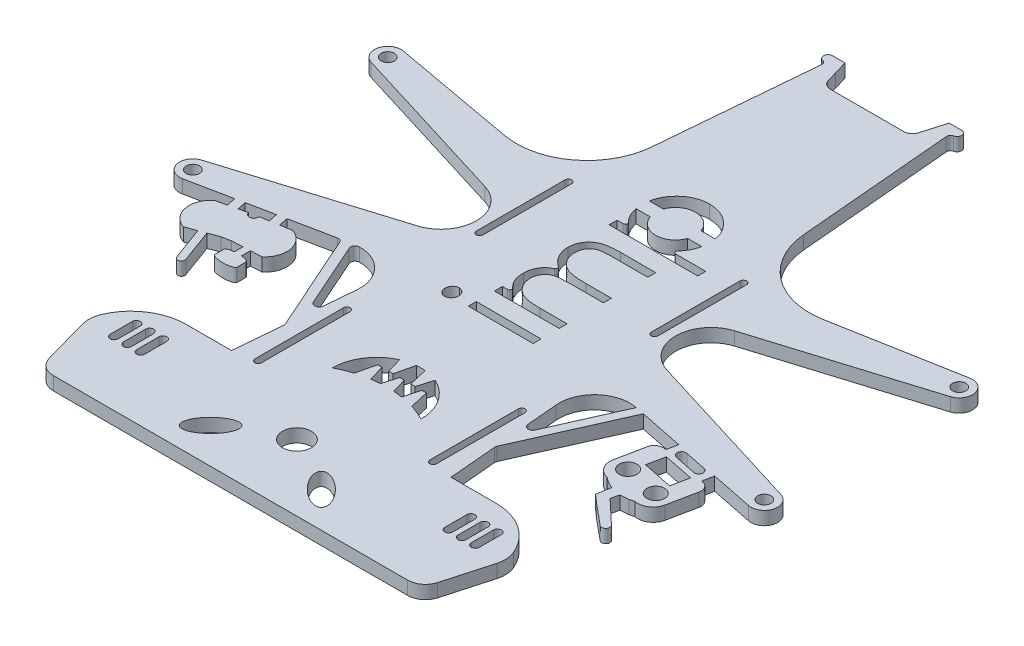
SolidWorks part; units mm, degrees
ref_plane "前视基准面" through (0, 0, 0) normal (0, 0, 1) x (1, 0, 0)
ref_plane "上视基准面" through (0, 0, 0) normal (0, 1, 0) x (1, 0, 0)
ref_plane "右视基准面" through (0, 0, 0) normal (1, 0, 0) x (0, 0, -1)
sketch "草图1" plane through (0, 0, 0) normal (0, 1, 0) x (1, 0, 0)
  line L5 (-65.3843, -19.1333) -> (-28.1418, -7.6445)
  line L6 (-63.9021, -24.9398) -> (-56.5526, -23.4451)
  line L8 (0, 0) -> (0, 91.5573) construction
  line L9 (0, 0) -> (-115.8836, 0) construction
  line L15 (0, 0) -> (0, -124.2991) construction
  line L16 (-15, -65) -> (15, -65) construction
  line L20 (-15.42, -115) -> (17.43, -115) construction
  line L21 (-28, -109.5) -> (-28, -90)
  line L22 (28, -109.5) -> (28, -90)
  line L23 (-17.5, -120) -> (17.5, -120)
  line L28 (22.5, -27) -> (22.5, 27) construction
  line L29 (-22.5, -27) -> (-22.5, 27) construction
  line L30 (28.1418, -7.6445) -> (65.3843, -19.1333)
  line L31 (28.1418, 7.6445) -> (65.3843, 19.1333)
  line L32 (-28, -90) -> (28, -90) construction
  line L33 (28, -90) -> (22.5, -27)
  line L34 (-28, -90) -> (-22.5, -27)
  line L36 (0, 0) -> (104.501, 0) construction
  line L37 (-28.1418, 7.6445) -> (-65.3843, 19.1333)
  line L39 (22.5, 70) -> (22.5, 27) construction
  line L40 (-22.5, 70) -> (-22.5, 27) construction
  line L41 (31.9307, 19.129) -> (63.9635, 24.9516) construction
  line L42 (-63.9635, 24.9516) -> (-31.9307, 19.129) construction
  line L43 (-17.1562, 34.2114) -> (-14.0779, 69.4717)
  line L44 (63.9635, 24.9516) -> (35.957, 19.8608)
  line L45 (-63.9635, 24.9516) -> (-35.957, 19.8608)
  line L46 (17.1562, 34.2114) -> (14.0779, 69.4717)
  line L51 (-49.203, -21.9504) -> (-47.2101, -31.7498) construction
  line L58 (-48.19, -31.9491) -> (-46.2301, -31.5505)
  line L59 (-41.8535, -20.4557) -> (-32.0641, -18.4647)
  line L65 (-14.4088, 65.6811) -> (14.4088, 65.6811) construction
  line L70 (-10.8845, 69.4717) -> (-10.1819, 67.1107)
  line L75 (10.8788, 69.4717) -> (10.1832, 67.115)
  line L76 (-8.265, 65.6811) -> (8.265, 65.6811)
  line L77 (-56.5526, -23.4451) -> (-41.8535, -20.4557) construction
  line L78 (-46.2301, -31.5505) -> (-43.7558, -31.4316)
  line L79 (-48.19, -31.9491) -> (-50.5246, -32.81)
  line L80 (-54.3603, -34.2244) -> (-39.6612, -31.235) construction
  line L81 (-48.7048, -24.4002) -> (-49.7844, -24.1095) construction
  line L82 (-48.7048, -24.4002) -> (-47.8245, -23.711) construction
  line L84 (41.8535, -20.4557) -> (32.0641, -18.4647)
  line L101 (-49.7844, -24.1095) -> (-47.8245, -23.711) construction
  line L103 (63.9021, -24.9398) -> (56.5526, -23.4451)
  line L106 (41.8535, -20.4557) -> (56.5526, -23.4451) construction
  line L107 (42.3935, -35.3623) -> (50.233, -36.9567) construction
  line L108 (39.6612, -31.235) -> (40.9566, -24.8654)
  line L109 (43.3151, -23.3041) -> (43.6091, -23.3639)
  line L110 (54.3603, -34.2244) -> (55.6557, -27.8548)
  line L111 (38.9637, -34.6648) -> (56.0543, -25.8949) construction
  line L112 (41.3552, -22.9055) -> (53.6628, -37.6542) construction
  line L113 (49.203, -21.9504) -> (41.4195, -60.2218) construction
  line L114 (43.6091, -23.3639) -> (44.8847, -23.1131) construction
  line L115 (44.8847, -23.1131) -> (52.7242, -24.7074) construction
  line L116 (52.7242, -24.7074) -> (53.8005, -25.4366) construction
  line L117 (53.8005, -25.4366) -> (54.0944, -25.4964)
  line L120 (44.938, -36.9003) -> (47.2899, -37.3786) construction
  line L121 (45.4995, -45.1782) -> (43.5396, -44.7797) construction
  line L122 (45.4995, -45.1782) -> (47.2899, -37.3786) construction
  line L123 (43.5396, -44.7797) -> (44.938, -36.9003) construction
  line L124 (43.2738, -36.0516) -> (49.1534, -37.2474) construction
  line L125 (47.2899, -37.3786) -> (49.1534, -37.2474)
  line L126 (44.938, -36.9003) -> (43.2738, -36.0516)
  line L127 (43.2738, -36.0516) -> (42.3935, -35.3623)
  line L128 (49.1534, -37.2474) -> (50.233, -36.9567)
  line L129 (43.1907, -31.4426) -> (51.0302, -33.0369) construction
  line L130 (40.7168, -24.8097) -> (55.8983, -27.8973) construction
  line L131 (52.7242, -24.7074) -> (53.1228, -22.7476) construction
  line L132 (44.8847, -23.1131) -> (45.2833, -21.1532) construction
  line L133 (53.1228, -22.7476) -> (56.5526, -23.4451) construction
  line L134 (41.8535, -20.4557) -> (45.2833, -21.1532) construction
  line L135 (45.6157, -39.5893) -> (53.5856, -46.6394) construction
  line L136 (44.3922, -39.9756) -> (46.3849, -41.7383)
  line L137 (46.8657, -39.2264) -> (47.8425, -40.0905)
  line L138 (47.8425, -40.0905) -> (46.3849, -41.7383) construction
  line L139 (47.2899, -37.3786) -> (46.8657, -39.2264)
  line L140 (44.938, -36.9003) -> (44.3922, -39.9756)
  line L141 (51.0114, -45.5639) -> (52.204, -44.2157) construction
  line L142 (47.8425, -40.0905) -> (52.204, -44.2157)
  line L143 (46.3849, -41.7383) -> (51.0114, -45.5639)
  line L144 (53.8005, -25.4366) -> (54.2987, -22.9867)
  line L145 (45.0757, -24.6826) -> (51.9353, -26.0777)
  line L146 (45.0757, -24.6826) -> (44.2785, -28.6024)
  line L147 (44.2785, -28.6024) -> (51.1381, -29.9975)
  line L148 (51.9353, -26.0777) -> (51.1381, -29.9975)
  line L149 (45.0757, -24.6826) -> (51.1381, -29.9975) construction
  line L150 (44.2785, -28.6024) -> (51.9353, -26.0777) construction
  line L151 (54.2987, -22.9867) -> (56.5526, -23.4451)
  line L152 (43.6091, -23.3639) -> (44.1073, -20.914)
  line L153 (41.8535, -20.4557) -> (44.1073, -20.914)
  line L154 (-47.8245, -23.711) -> (-45.8523, -23.3727)
  line L155 (-49.7844, -24.1095) -> (-51.732, -24.5684)
  line L156 (-56.1141, -25.601) -> (-48.1766, -23.9867) construction
  line L157 (-52.91, -29.4394) -> (-42.8653, -27.3966) construction
  line L158 (-42.9558, -31.3932) -> (-42.9558, -37.0074) construction
  line L159 (-51.2752, -33.0867) -> (-49.3498, -38.3078) construction
  line L160 (-49.3498, -38.3078) -> (-42.9558, -37.0074) construction
  line L161 (-41.8535, -20.4557) -> (-44.3033, -20.9539)
  line L162 (-44.3033, -20.9539) -> (-43.8802, -23.0344)
  line L163 (-45.8523, -23.3727) -> (-46.2632, -21.3525)
  line L164 (-56.5526, -23.4451) -> (-54.1027, -22.9469)
  line L165 (-54.1027, -22.9469) -> (-53.6796, -25.0273)
  line L166 (-51.732, -24.5684) -> (-52.1428, -22.5483)
  line L167 (-52.1428, -22.5483) -> (-46.2632, -21.3525)
  line L168 (-53.6796, -25.0273) -> (-56.1141, -25.601)
  line L169 (-43.8802, -23.0344) -> (-41.415, -22.6115)
  line L170 (-43.7558, -31.4316) -> (-43.7558, -33.3548)
  line L171 (-42.1558, -31.3548) -> (-42.1558, -33.3548)
  line L172 (-42.1558, -31.3548) -> (-39.6612, -31.235)
  line L173 (-45.4558, -34.0654) -> (-40.4558, -34.0654) construction
  line L174 (-42.9558, -34.8154) -> (-42.9558, -33.3154) construction
  line L175 (-45.4558, -36.0654) -> (-40.4558, -36.0654) construction
  line L176 (-42.9558, -36.8154) -> (-42.9558, -35.3154) construction
  line L177 (-40.4558, -36.0654) -> (-40.4558, -34.0654)
  line L178 (-45.4558, -36.0654) -> (-45.4558, -34.0654)
  line L179 (-50.5246, -32.81) -> (-47.7567, -40.3159)
  line L180 (-52.0257, -33.3635) -> (-49.2579, -40.8695)
  line L181 (-52.0257, -33.3635) -> (-54.3603, -34.2244)
  line L182 (11.7642, 72.4717) -> (14.5779, 72.4717)
  line L183 (-11.7642, 72.4717) -> (-14.5779, 72.4717)
  line L184 (11.7642, 72.4717) -> (10.8788, 69.4717)
  line L185 (-11.7642, 72.4717) -> (-10.8845, 69.4717)
  line L186 (46.5041, -22.6771) -> (51.4037, -23.6735) construction
  line L187 (46.7033, -21.6971) -> (51.603, -22.6936)
  line L188 (46.3048, -23.657) -> (51.2045, -24.6535)
  circle A0 centre (-64.5, 30) radius 1.5 construction
  circle A1 centre (64.5, 30) radius 1.5 construction
  circle A2 centre (64.5, -30) radius 1.5 construction
  circle A3 centre (-64.5, -30) radius 1.5 construction
  circle A4 centre (-64.5, 30) radius 3 construction
  circle A5 centre (64.5, 30) radius 3 construction
  circle A6 centre (64.5, -30) radius 3 construction
  circle A7 centre (-64.5, -30) radius 3 construction
  circle A10 centre (-64.5, 22) radius 1.5
  circle A11 centre (64.5, 22) radius 1.5
  circle A12 centre (64.5, -22) radius 1.5
  circle A13 centre (-64.5, -22) radius 1.5
  circle A22 centre (0, -90) radius 25
  circle A23 centre (-15, -65) radius 1
  circle A24 centre (15, -65) radius 1
  circle A25 centre (-15.42, -115) radius 1
  circle A26 centre (17.43, -115) radius 1
  arc A27 (-17.5, -120) -> (-28, -109.5) centre (-17.5, -109.5) cw
  arc A28 (17.5, -120) -> (28, -109.5) centre (17.5, -109.5) ccw
  arc A42 (63.9021, -24.9398) -> (65.3843, -19.1333) centre (64.5, -22) ccw
  arc A43 (65.3843, 19.1333) -> (63.9635, 24.9516) centre (64.5, 22) ccw
  arc A44 (28.1418, -7.6445) -> (28.1418, 7.6445) centre (30.5, 0) cw
  arc A47 (-65.3843, -19.1333) -> (-63.9021, -24.9398) centre (-64.5, -22) ccw
  arc A49 (-28.1418, -7.6445) -> (-28.1418, 7.6445) centre (-30.5, 0) ccw
  arc A50 (-22.5, -27) -> (-32.0641, -18.4647) centre (-30.4697, -26.3042) ccw
  arc A51 (-63.9635, 24.9516) -> (-65.3843, 19.1333) centre (-64.5, 22) ccw
  arc A52 (31.9307, 19.129) -> (22.5, 27) centre (30.5, 27) cw construction
  arc A53 (-31.9307, 19.129) -> (-22.5, 27) centre (-30.5, 27) ccw construction
  arc A54 (-35.957, 19.8608) -> (-17.1562, 34.2114) centre (-33.0955, 35.6029) ccw
  arc A55 (17.1562, 34.2114) -> (35.957, 19.8608) centre (33.0955, 35.6029) ccw
  arc A56 (-8.265, 65.6811) -> (-10.1819, 67.1107) centre (-8.265, 67.6811) cw
  arc A57 (10.1832, 67.115) -> (8.265, 65.6811) centre (8.265, 67.6811) cw
  arc A79 (22.5, -27) -> (32.0641, -18.4647) centre (30.4697, -26.3042) cw
  arc A80 (55.6557, -27.8548) -> (54.0944, -25.4964) centre (53.6959, -27.4562) ccw
  arc A81 (40.9566, -24.8654) -> (43.3151, -23.3041) centre (42.9165, -25.264) cw
  arc A83 (43.5396, -44.7797) -> (45.4995, -45.1782) centre (44.5196, -44.9789) ccw construction
  arc A84 (54.3603, -34.2244) -> (50.233, -36.9567) centre (50.9305, -33.5269) cw
  arc A85 (39.6612, -31.235) -> (42.3935, -35.3623) centre (43.091, -31.9325) ccw
  circle A86 centre (43.1907, -31.4426) radius 2
  circle A87 centre (51.0302, -33.0369) radius 2
  arc A88 (44.8847, -23.1131) -> (41.8535, -20.4557) centre (40.7168, -24.8097) ccw construction
  arc A89 (52.7242, -24.7074) -> (56.5526, -23.4451) centre (55.8983, -27.8973) cw construction
  arc A90 (51.0114, -45.5639) -> (52.204, -44.2157) centre (51.6077, -44.8898) ccw
  arc A91 (-39.6612, -31.235) -> (-41.415, -22.6115) centre (-42.8653, -27.3966) ccw
  arc A92 (-54.3603, -34.2244) -> (-56.1141, -25.601) centre (-52.91, -29.4394) cw
  arc A93 (-49.2579, -40.8695) -> (-47.7567, -40.3159) centre (-48.5073, -40.5927) ccw
  arc A94 (14.5779, 72.4717) -> (14.7779, 70.4717) centre (14.5779, 71.4617) cw
  arc A95 (14.0779, 69.4717) -> (14.7779, 70.4717) centre (14.9532, 69.604) cw
  arc A96 (-14.0779, 69.4717) -> (-14.7779, 70.4717) centre (-14.9532, 69.604) ccw
  arc A97 (-14.5779, 72.4717) -> (-14.7779, 70.4717) centre (-14.5779, 71.4617) ccw
  arc A98 (-49.7844, -24.1095) -> (-47.8245, -23.711) centre (-48.8044, -23.9103) ccw
  arc A99 (46.7033, -21.6971) -> (46.3048, -23.657) centre (46.5041, -22.6771) ccw
  arc A100 (51.2045, -24.6535) -> (51.603, -22.6936) centre (51.4037, -23.6735) ccw
  ellipse E0 centre (-42.9558, -36.0654) end of major axis (-40.4558, -36.0654) minor radius 0.75 (-45.4558, -36.0654) -> (-40.4558, -36.0654) ccw
  ellipse E1 centre (-42.9558, -34.0654) end of major axis (-45.4558, -34.0654) minor radius 0.75 (-40.4558, -34.0654) -> (-42.1558, -33.3548) ccw
  ellipse E2 centre (-42.9558, -34.0654) end of major axis (-45.4558, -34.0654) minor radius 0.75 (-43.7558, -33.3548) -> (-45.4558, -34.0654) ccw
  point P0 (0, 0)
  point P55 (47.509, -30.2799)
  point P109 (-9.7565, 65.6811)
  point P112 (9.76, 65.6811)
  point P182 (48.1069, -27.34)
  point P213 (48.9539, -23.1753)
  dimension "D1" = 3
  dimension "D6" = 6
  dimension "D7" = 6
  dimension "D8" = 6
  dimension "D9" = 6
  dimension "D15" = 3
  dimension "D18" = 6
  dimension "D19" = 16
  dimension "D20" = 8
  dimension "D21" = 22
  dimension "D22" = 50
  dimension "D28" = 2
  dimension "D31" = 2
  dimension "D25" = 45
  dimension "D37" = 27
  dimension "D38" = 16
  dimension "D39" = 15
  dimension "D40" = 12
  dimension "D41" = 6
  dimension "D44" = 8
  dimension "D45" = 5.2
  dimension "D27" = 22.5
  dimension "D47" = 10.5
  dimension "D48" = 15
  dimension "D17" = 8
  dimension "D12" = 6
  dimension "D13" = 8
  dimension "D16" = 8
  dimension "D60" = 2
  dimension "D61" = 2
  dimension "D62" = 1
  dimension "D67" = 7.5
  dimension "D70" = 0.2
  dimension "D74" = 6
  dimension "D77" = 0.8
  dimension "D81" = 2.4
  dimension "D66" = 2
  dimension "D86" = 1
  dimension "D90" = 3
  dimension "D93" = 2
  dimension "D79" = 2.4743
  dimension "D82" = 1
  dimension "D87" = 1
  dimension "D91" = 3.5
  dimension "D92" = 3.5
  dimension "D102" = 4
  dimension "D103" = 4.5
  dimension "D114" = 0.9
  dimension "D68" = 5
  dimension "D69" = 5
  dimension "D78" = 5
  dimension "D130" = 0.5
  dimension "D96" = 1
  dimension "D2" = 129
  dimension "D3" = 60
  dimension "D4" = 30
  dimension "D5" = 64.5
  dimension "D11" = 27
  dimension "D14" = 9.7565
  dimension "D23" = 30
  dimension "D24" = 15
  dimension "D26" = 30
  dimension "D29" = 32.85
  dimension "D30" = 2.43
  dimension "D32" = 27
  dimension "D33" = 28
  dimension "D34" = 28
  dimension "D35" = 35
  dimension "D36" = 17.5
  dimension "D42" = 45
  dimension "D43" = 5.2
  dimension "D46" = 120
  dimension "D49" = 2.4933
  dimension "D50" = 2
  dimension "D51" = 1
  dimension "D52" = 15
  dimension "D53" = 7.5
  dimension "D54" = 0.5
  dimension "D55" = 4
  dimension "D56" = 4
  dimension "D57" = 65.6811
  dimension "D58" = 10.1819
  dimension "D59" = 10.1832
  dimension "D63" = 2
  dimension "D64" = 0.8
  dimension "D65" = 15
  dimension "D71" = 8
  dimension "D72" = 2
  dimension "D73" = 2.5
  dimension "D75" = 5
  dimension "D76" = 2
  dimension "D80" = 2
  dimension "D83" = 8
  dimension "D84" = 1.2
  dimension "D85" = 1
  dimension "D88" = 0.5
  dimension "D89" = 3
  dimension "D94" = 4
  dimension "D95" = 4
  dimension "D97" = 8.265
  dimension "D98" = 3.7906
  dimension "D99" = 8.265
  dimension "D100" = 9.76
  dimension "D101" = 22.5
  dimension "D104" = 60
  dimension "D105" = 10.8845
  dimension "D106" = 10.8788
  dimension "D107" = 2.5
  dimension "D108" = 1.1
  dimension "D109" = 1.1
  dimension "D110" = 2
  dimension "D111" = 0.9
  dimension "D112" = 0.9
  dimension "D113" = 6
  dimension "D115" = 4
  dimension "D116" = 7
  dimension "D117" = 1.5
  dimension "D118" = 5
  dimension "D119" = 1.5
  dimension "D120" = 1.5
  dimension "D121" = 2
  dimension "D122" = 2
  dimension "D123" = 1.6
  dimension "D124" = 0.8
  dimension "D125" = 8
  dimension "D126" = 2.4882
  dimension "D127" = 3
  dimension "D128" = 0.2
  dimension "D129" = 1
  dimension "D131" = 1.25
  dimension "D132" = 2
  dimension "D133" = 5
extrude "凸台-拉伸1" add sketch "草图1" along normal blind 3
sketch "草图2" plane through (0, 0, 0) normal (0, -1, 0) x (1, 0, 0)
  line L0 (0, 133.3282) -> (0, -97.043) construction
  line L1 (-19.75, 2) -> (-19.75, -18) construction
  line L2 (-19, 2) -> (-19, -18)
  line L3 (-20.5, 2) -> (-20.5, -18)
  line L4 (19.75, 2) -> (19.75, -18) construction
  line L5 (20.5, 2) -> (20.5, -18)
  line L6 (19, 2) -> (19, -18)
  line L7 (0, 0) -> (56.7659, 0) construction
  line L8 (-19.75, 52) -> (-19.75, 32) construction
  line L9 (-19, 52) -> (-19, 32)
  line L10 (-20.5, 52) -> (-20.5, 32)
  line L11 (19.75, 52) -> (19.75, 32) construction
  line L12 (20.5, 52) -> (20.5, 32)
  line L13 (19, 52) -> (19, 32)
  arc A0 (-19, 2) -> (-20.5, 2) centre (-19.75, 2) ccw
  arc A1 (-20.5, -18) -> (-19, -18) centre (-19.75, -18) ccw
  arc A2 (20.5, 2) -> (19, 2) centre (19.75, 2) ccw
  arc A3 (19, -18) -> (20.5, -18) centre (19.75, -18) ccw
  arc A4 (-19, 52) -> (-20.5, 52) centre (-19.75, 52) ccw
  arc A5 (-20.5, 32) -> (-19, 32) centre (-19.75, 32) ccw
  arc A6 (20.5, 52) -> (19, 52) centre (19.75, 52) ccw
  arc A7 (19, 32) -> (20.5, 32) centre (19.75, 32) ccw
  arc A8 (-10, 45) -> (10, 45) centre (0, 45) ccw
  arc A9 (-10, 45) -> (10, 45) centre (0, 64.5959) ccw
  point P5 (-19.75, -8)
  point P10 (19.75, -8)
  point P19 (-19.75, 42)
  point P26 (19.75, 42)
  dimension "D6" = 42
  dimension "D8" = 10
  dimension "D9" = 22
  dimension "D1" = 1.5
  dimension "D2" = 20
  dimension "D3" = 19
  dimension "D4" = 19
  dimension "D5" = 8
  dimension "D7" = 45
  dimension "D10" = 10
extrude "切除-拉伸1" cut sketch "草图2" against normal blind 3
sketch "草图3" plane through (0, 0, 0) normal (0, -1, 0) x (1, 0, 0)
  line L0 (0, 67.5428) -> (0, 35) construction
  line L1 (-5, 60.2388) -> (-5, 35) construction
  line L2 (5, 60.0167) -> (5, 35) construction
  line L3 (-1.5, 42.6471) -> (-0.5, 39.2959)
  line L4 (0.5, 39.2959) -> (1.5, 42.6471)
  line L5 (-5, 38.7959) -> (5, 38.7959) construction
  line L6 (-4.5, 39.2959) -> (-3.5, 42.8761)
  line L7 (-6.5, 43.5781) -> (-5.5, 39.2959)
  line L8 (4.5, 39.2959) -> (3.5, 42.8761)
  line L9 (5.5, 39.2959) -> (6.5, 43.5781)
  line L10 (-5, 42.5959) -> (5, 42.5959) construction
  line L11 (-5, 35) -> (5, 35) construction
  line L12 (-2.5, 42.5959) -> (-2.5, 44.2103) construction
  line L13 (2.5, 42.5959) -> (2.5, 33.8348) construction
  line L14 (-2, 39.2959) -> (-1, 35.0501)
  line L15 (-3, 39.2959) -> (-4, 35.8348)
  line L16 (2, 39.2959) -> (1, 35.0501)
  line L17 (3, 39.2959) -> (4, 35.8348)
  line L18 (-6.5, 43.5781) -> (-6.5, 44.5781)
  line L19 (-6.5, 44.5781) -> (6.5, 44.5781)
  line L20 (6.5, 44.5781) -> (6.5, 43.5781)
  line L21 (-3.5, 42.8761) -> (-3.5, 43.8761)
  line L22 (-3.5, 43.8761) -> (-1.5, 43.8761)
  line L23 (-1.5, 43.8761) -> (-1.5, 42.6471)
  line L24 (1.5, 42.6471) -> (1.5, 43.8761)
  line L25 (1.5, 43.8761) -> (3.5, 43.8761)
  line L26 (3.5, 43.8761) -> (3.5, 42.8761)
  line L27 (-4, 35.8348) -> (-4, 33.8348)
  line L28 (-4, 33.8348) -> (4, 33.8348)
  line L29 (4, 33.8348) -> (4, 35.8348)
  line L30 (-1, 35.0501) -> (-1, 34.0501)
  line L31 (-1, 34.0501) -> (1, 34.0501)
  line L32 (1, 34.0501) -> (1, 35.0501)
  line L33 (-5.5, 39.2959) -> (-4.5, 39.2959)
  line L34 (-0.5, 39.2959) -> (0.5, 39.2959)
  line L35 (4.5, 39.2959) -> (5.5, 39.2959)
  line L36 (-3, 39.2959) -> (-2, 39.2959)
  line L37 (2, 39.2959) -> (3, 39.2959)
  arc A0 (-10, 45) -> (10, 45) centre (0, 64.5959) ccw construction
  arc A1 (-10, 45) -> (10, 45) centre (0, 64.5959) ccw construction
  arc A2 (-10, 45) -> (10, 45) centre (0, 45) ccw construction
  arc A3 (-10, 45) -> (10, 45) centre (0, 45) ccw construction
  dimension "D21" = 0.5
  dimension "D25" = 0.5
  dimension "D26" = 1
  dimension "D28" = 1
  dimension "D33" = 0.5
  dimension "D1" = 5
  dimension "D2" = 5
  dimension "D3" = 7.5959
  dimension "D4" = 3
  dimension "D5" = 1.5
  dimension "D6" = 1.5
  dimension "D7" = 1.5
  dimension "D8" = 3
  dimension "D9" = 1.5
  dimension "D10" = 3.8
  dimension "D11" = 2.5
  dimension "D12" = 5
  dimension "D13" = 1.5
  dimension "D14" = 1.5
  dimension "D15" = 1.5
  dimension "D16" = 1.5
  dimension "D17" = 1
  dimension "D18" = 1
  dimension "D19" = 1
  dimension "D20" = 2
  dimension "D22" = 0.5
  dimension "D23" = 0.5
  dimension "D24" = 1
  dimension "D27" = 0.5
  dimension "D29" = 0.5
  dimension "D30" = 1
  dimension "D31" = 0.5
  dimension "D32" = 1
extrude "凸台-拉伸2" add sketch "草图3" against normal blind 3
sketch "草图4" plane through (0, 0, 0) normal (0, -1, 0) x (1, 0, 0)
  line L0 (0, 0) -> (0, 140.5969) construction
  line L1 (-28, 108) -> (-21.4476, 108)
  line L2 (-17.5, 120) -> (17.5, 120) construction
  line L3 (-28, 90) -> (28, 90) construction
  line L4 (-28, 90) -> (-28, 109.5) construction
  line L5 (28, 109.5) -> (28, 90) construction
  line L6 (-21.4476, 114) -> (-21.4476, 119.2297)
  line L7 (21.4476, 119.2297) -> (21.4476, 114)
  line L8 (21.4476, 108) -> (28, 108)
  line L9 (-21.4476, 114) -> (-26.9868, 114)
  line L10 (21.4476, 114) -> (26.9868, 114)
  line L11 (-28, 108) -> (-28, 90)
  line L12 (28, 108) -> (28, 90)
  circle A0 centre (0, 90) radius 25 construction
  circle A1 centre (0, 90) radius 25 construction
  arc A2 (-21.4476, 108) -> (-28, 90) centre (0, 90) ccw
  arc A3 (28, 90) -> (21.4476, 108) centre (0, 90) ccw
  arc A4 (-17.5, 120) -> (-28, 109.5) centre (-17.5, 109.5) ccw construction
  arc A5 (28, 109.5) -> (17.5, 120) centre (17.5, 109.5) ccw construction
  arc A6 (-21.4476, 119.2297) -> (-26.9868, 114) centre (-17.5, 109.5) ccw
  arc A7 (26.9868, 114) -> (21.4476, 119.2297) centre (17.5, 109.5) ccw
  dimension "D1" = 12
  dimension "D4" = 6
  dimension "D5" = 6
extrude "切除-拉伸2" cut sketch "草图4" against normal blind 3
sketch "草图6" plane through (0, 0, 0) normal (0, -1, 0) x (1, 0, 0)
  line L0 (-21.4476, 119.2297) -> (-21.4476, 139)
  line L1 (-18.4476, 142) -> (18.4476, 142)
  line L2 (21.4476, 139) -> (21.4476, 119.2297)
  line L3 (-17.5, 120) -> (17.5, 120) construction
  line L4 (0, 0) -> (0, 166.5632) construction
  line L5 (-21.4476, 131) -> (21.4476, 131) construction
  line L6 (-21.4476, 139) -> (-18.4476, 142)
  line L7 (18.4476, 142) -> (21.4476, 139)
  line L8 (-21.4476, 119.2297) -> (21.4476, 119.2297)
  circle A0 centre (0, 131) radius 3.25
  point P1 (-21.4476, 142)
  point P4 (21.4476, 142)
  dimension "D3" = 6.5
  dimension "D1" = 22
  dimension "D2" = 11
extrude "凸台-拉伸3" add sketch "草图6" against normal blind 3
sketch "草图7" plane through (0, 0, 0) normal (0, -1, 0) x (1, 0, 0)
  line L0 (-21.4476, 108) -> (-28, 108) construction
  line L1 (-21.4476, 108) -> (-28, 108) construction
  line L2 (28, 108) -> (21.4476, 108) construction
  line L3 (28, 108) -> (21.4476, 108) construction
  line L4 (-22.5, 27) -> (-28, 90) construction
  line L5 (-26.6119, 74.1001) -> (-28, 90)
  line L6 (28, 90) -> (22.5, 27) construction
  line L7 (28, 90) -> (26.6119, 74.1001)
  line L8 (-25.2389, 108) -> (-21.4476, 108)
  line L9 (21.4476, 108) -> (25.2389, 108)
  circle A0 centre (0, 90) radius 25 construction
  circle A1 centre (0, 90) radius 25 construction
  arc A2 (-25.2389, 108) -> (-26.6119, 74.1001) centre (0, 90) ccw
  arc A3 (26.6119, 74.1001) -> (25.2389, 108) centre (0, 90) ccw
  arc A4 (-21.4476, 108) -> (-28, 90) centre (0, 90) ccw construction
  arc A5 (-21.4476, 108) -> (-28, 90) centre (0, 90) ccw
  arc A6 (28, 90) -> (21.4476, 108) centre (0, 90) ccw construction
  arc A7 (28, 90) -> (21.4476, 108) centre (0, 90) ccw
  dimension "D1" = 62
extrude "凸台-拉伸4" add sketch "草图7" against normal blind 3
sketch "草图8" plane through (0, 3, 0) normal (0, 1, 0) x (1, 0, 0)
  line L0 (7.8825, -19.3796) -> (7.8825, 18.6946) construction
  text T0 "imp" font "Century Gothic" height 20
  dimension "D1" = 7.8825
  dimension "D2" = 19.3796
extrude "切除-拉伸3" cut sketch "草图8" against normal blind 10 body kept at (44.938, 0, 36.9003)
sketch "草图10" plane through (0, 0, 0) normal (0, -1, 0) x (1, 0, 0)
  line L0 (-26.9868, 114) -> (-31.4868, 114)
  line L2 (-31.4868, 108) -> (-26.9868, 108)
  line L3 (-26.9868, 108) -> (-26.9868, 114)
  line L4 (-25.2389, 108) -> (-28, 108) construction
  line L5 (0, 0) -> (0, 153.1529) construction
  line L10 (26.9868, 108) -> (26.9868, 114)
  line L11 (31.4868, 108) -> (26.9868, 108)
  line L12 (26.9868, 114) -> (31.4868, 114)
  arc A0 (-31.4868, 114) -> (-31.4868, 108) centre (-29.2368, 111) ccw
  arc A1 (31.4868, 114) -> (31.4868, 108) centre (29.2368, 111) cw
  dimension "D1" = 3.75
  dimension "D2" = 4.5
  dimension "D3" = 4.5
extrude "凸台-拉伸6" add sketch "草图10" against normal blind 3
fillet "圆角2" radius 2 1 edges at (-21.4476, 1.5, 114)
fillet "圆角3" radius 2 1 edges at (21.4476, 1.5, 114)
fillet "圆角4" radius 1 1 edges at (-25.2389, 1.5, 108)
fillet "圆角5" radius 1 1 edges at (25.2389, 1.5, 108)
sketch "草图11" plane through (0, 0, 0) normal (0, -1, 0) x (1, 0, 0)
  line L0 (-22.5, 27) -> (-26.6119, 74.1001) construction
  line L1 (-22.5, 27) -> (-26.6119, 74.1001) construction
  line L2 (-44.3033, 20.9539) -> (-32.0641, 18.4647) construction
  line L3 (-44.3033, 20.9539) -> (-32.0641, 18.4647) construction
  line L4 (-32.0641, 18.4647) -> (-23.4449, 37.8236)
  line L5 (-32.0641, 18.4647) -> (30.3166, 18.4647) construction
  line L6 (-23.8038, 41.9347) -> (-34.0716, 18.873)
  line L7 (-23.8038, 41.9347) -> (-23.4449, 37.8236)
  line L8 (-34.0716, 18.873) -> (-32.0641, 18.4647)
  line L9 (0, 0) -> (0, 75.6123) construction
  line L10 (34.0716, 18.873) -> (32.0641, 18.4647)
  line L11 (23.8038, 41.9347) -> (23.4449, 37.8236)
  line L12 (23.8038, 41.9347) -> (34.0716, 18.873)
  line L13 (32.0641, 18.4647) -> (23.4449, 37.8236)
  dimension "D1" = 66
  dimension "D2" = 2
extrude "凸台-拉伸7" add sketch "草图11" against normal blind 3
fillet "圆角6" radius 1 1 edges at (23.8038, 1.5, 41.9347)
fillet "圆角7" radius 1 1 edges at (23.4449, 1.5, 37.8236)
fillet "圆角11" radius 1 1 edges at (-23.8038, 1.5, 41.9347)
fillet "圆角12" radius 1 1 edges at (-34.0716, 1.5, 18.873)
fillet "圆角13" radius 1 1 edges at (-23.4449, 1.5, 37.8236)
fillet "圆角14" radius 1 1 edges at (-32.0641, 1.5, 18.4647)
fillet "圆角22" radius 0.5 1 edges at (-4.1928, 1.5, 9.8924)
fillet "圆角23" radius 0.5 1 edges at (-3.4596, 1.5, 0.2009)
fillet "圆角24" radius 0.5 1 edges at (-4.0286, 1.5, -16.0051)
fillet "圆角25" radius 0.5 1 edges at (5.2343, 1.5, -16.0051)
ref_plane "基准面1" through (-5.1944, 0, -4.8472) normal (-0.0288, 0, 0.9996) x (0.9996, 0, 0.0288)
sketch "草图13" plane through (0, 0, 0) normal (0, -1, 0) x (1, 0, 0)
  line L0 (-6.9893, -21.9105) -> (8.1374, -21.9105) construction
  line L1 (0.5607, -29.5941) -> (0.5607, -14.2102) construction
  line L2 (4.8034, -20.4105) -> (9.8034, -20.4105)
  line L3 (9.8034, -20.4105) -> (9.8034, -23.4105)
  line L4 (9.8034, -23.4105) -> (4.8034, -23.4105)
  line L5 (13.2671, -14.2102) -> (-6.7329, -14.2102) construction
  line L6 (-8.6819, -20.4105) -> (-8.6819, -23.4105)
  line L7 (-8.6819, -23.4105) -> (-3.6819, -23.4105)
  line L8 (-3.6819, -20.4105) -> (-8.6819, -20.4105)
  arc A0 (4.8034, -20.4105) -> (-3.6819, -20.4105) centre (0.5607, -21.9105) ccw
  arc A1 (-3.6819, -23.4105) -> (4.8034, -23.4105) centre (0.5607, -21.9105) ccw
  spline S1 degree 3 poles (-5.0243, -16.8582) (-5.1415, -16.9756) (-5.4461, -17.3038) (-5.8828, -17.8811) (-6.2972, -18.6036) (-6.6033, -19.3734) (-6.8311, -20.1796) (-6.9649, -21.0313) (-6.9811, -21.6136) (-6.9893, -21.9105) knots 0.190736 0.190736 0.190736 0.190736 0.26303 0.385707 0.505717 0.625137 0.74612 0.870524 1 1 1 1 construction
  spline S3 degree 3 poles (8.1389, -21.9666) (8.1309, -21.6763) (8.1152, -21.103) (7.9754, -20.2624) (7.7458, -19.4571) (7.4239, -18.6894) (7.0104, -17.9571) (6.5671, -17.3461) (6.2548, -16.9858) (6.1245, -16.846) knots 0 0 0 0 0.126833 0.250437 0.371271 0.492148 0.613426 0.738014 0.821523 0.821523 0.821523 0.821523 construction
  spline S4 degree 3 poles (0.5347, -29.5948) (0.7942, -29.5878) (1.3058, -29.574) (2.0572, -29.4669) (2.78, -29.2957) (3.473, -29.0496) (4.1358, -28.7317) (4.7678, -28.3448) (5.3689, -27.8883) (5.9309, -27.3666) (6.4486, -26.8006) (6.9014, -26.1956) (7.2817, -25.5609) (7.5993, -24.9) (7.8387, -24.207) (8.0113, -23.4852) (8.1178, -22.735) (8.1318, -22.2247) (8.1389, -21.9666) knots 0 0 0 0 0.064921 0.128034 0.189574 0.25058 0.311733 0.37325 0.435763 0.500346 0.564949 0.627528 0.689157 0.749865 0.81076 0.8723 0.935413 1 1 1 1 construction
  dimension "D1" = 9
  dimension "D2" = 3
  dimension "D3" = 7.7003
  dimension "D4" = 15.1267
  dimension "D5" = 7.55
  dimension "D6" = 1.5
  dimension "D7" = 5
extrude "凸台-拉伸8" add sketch "草图13" against normal blind 3
sketch "草图14" plane through (0, 0, 0) normal (0, -1, 0) x (1, 0, 0)
  line L1 (50, 63) -> (-50, 63)
  line L2 (50, 63) -> (50, 163)
  line L3 (50, 163) -> (-50, 163)
  line L4 (-50, 63) -> (-50, 163)
  line L5 (50, 63) -> (-50, 163) construction
  line L6 (50, 163) -> (-50, 63) construction
  point P0 (0, 113)
  point P5 (0, 0)
  dimension "D1" = 63
  dimension "D2" = 100
  dimension "D3" = 100
extrude "切除-拉伸4" cut sketch "草图14" against normal blind 10
sketch "草图15" plane through (0, 0, 0) normal (0, -1, 0) x (1, 0, 0)
  line L0 (-47, 63) -> (47, 63) construction
  line L1 (-25.6429, 63) -> (25.6429, 63) construction
  line L2 (-40, 78) -> (40, 78)
  line L3 (-35, 53) -> (35, 53)
  line L4 (0, 0) -> (0, 78) construction
  line L9 (-44, 66) -> (44, 66) construction
  line L10 (-44, 60) -> (44, 60) construction
  line L11 (-44, 66) -> (-44, 60) construction
  line L12 (-43.8522, 75.0775) -> (-46.7782, 64.6162)
  line L13 (43.8522, 75.0775) -> (46.7782, 64.6162)
  arc A8 (-46.5385, 60.6923) -> (-46.7782, 64.6162) centre (-41, 63) cw
  arc A9 (46.5385, 60.6923) -> (46.7782, 64.6162) centre (41, 63) ccw
  arc A10 (-35, 53) -> (-46.5385, 60.6923) centre (-35, 65.5) cw
  arc A11 (35, 53) -> (46.5385, 60.6923) centre (35, 65.5) ccw
  arc A12 (-40, 78) -> (-43.8522, 75.0775) centre (-40, 74) ccw
  arc A13 (40, 78) -> (43.8522, 75.0775) centre (40, 74) cw
  circle A14 centre (0, 63) radius 3.25
  dimension "D9" = 6
  dimension "D10" = 6
  dimension "D11" = 6
  dimension "D12" = 6
  dimension "D13" = 3
  dimension "D15" = 4
  dimension "D16" = 6.5
  dimension "D1" = 15
  dimension "D2" = 10
  dimension "D3" = 70
  dimension "D4" = 35
  dimension "D5" = 80
  dimension "D6" = 40
  dimension "D7" = 94
  dimension "D8" = 47
  dimension "D14" = 3
extrude "凸台-拉伸9" add sketch "草图15" against normal blind 3
sketch "草图16" plane through (0, 0, 0) normal (0, -1, 0) x (1, 0, 0)
  line L0 (0, 63) -> (0, 78) construction
  line L1 (40, 78) -> (-40, 78) construction
  line L2 (-45.2723, 70) -> (45.2723, 70) construction
  line L3 (-43.8522, 75.0775) -> (-46.7782, 64.6162) construction
  line L4 (46.7782, 64.6162) -> (43.8522, 75.0775) construction
  line L5 (-12.5, 78) -> (-12.5, 53) construction
  line L6 (12.5, 78) -> (12.5, 53) construction
  line L7 (-16.0355, 73.5355) -> (-8.9645, 66.4645) construction
  line L8 (-10.909, 71.591) -> (-14.091, 68.409) construction
  line L9 (-35, 53) -> (-24.7698, 53) construction
  line L10 (-46.6619, 61) -> (46.6619, 61) construction
  line L11 (-40.7619, 63.5) -> (-40.7619, 58.5) construction
  line L12 (-39.8619, 63.5) -> (-39.8619, 58.5)
  line L13 (-41.6619, 63.5) -> (-41.6619, 58.5)
  line L14 (-37.7619, 63.5) -> (-37.7619, 58.5) construction
  line L15 (-36.8619, 63.5) -> (-36.8619, 58.5)
  line L16 (-38.6619, 63.5) -> (-38.6619, 58.5)
  line L17 (-34.7619, 63.5) -> (-34.7619, 58.5) construction
  line L18 (-33.8619, 63.5) -> (-33.8619, 58.5)
  line L19 (-35.6619, 63.5) -> (-35.6619, 58.5)
  line L20 (34.7619, 63.5) -> (34.7619, 58.5) construction
  line L21 (33.8619, 63.5) -> (33.8619, 58.5)
  line L22 (35.6619, 63.5) -> (35.6619, 58.5)
  line L23 (37.7619, 63.5) -> (37.7619, 58.5) construction
  line L24 (36.8619, 63.5) -> (36.8619, 58.5)
  line L25 (38.6619, 63.5) -> (38.6619, 58.5)
  line L26 (40.7619, 63.5) -> (40.7619, 58.5) construction
  line L27 (39.8619, 63.5) -> (39.8619, 58.5)
  line L28 (41.6619, 63.5) -> (41.6619, 58.5)
  arc A0 (3.25, 63) -> (-3.25, 63) centre (0, 63) ccw construction
  arc A1 (3.25, 63) -> (-3.25, 63) centre (0, 63) ccw construction
  circle A2 centre (0, 63) radius 3.25
  arc A3 (-46.5385, 60.6923) -> (-35, 53) centre (-35, 65.5) ccw construction
  arc A4 (35, 53) -> (46.5385, 60.6923) centre (35, 65.5) ccw construction
  arc A5 (-39.8619, 63.5) -> (-41.6619, 63.5) centre (-40.7619, 63.5) ccw
  arc A6 (-41.6619, 58.5) -> (-39.8619, 58.5) centre (-40.7619, 58.5) ccw
  arc A7 (-36.8619, 63.5) -> (-38.6619, 63.5) centre (-37.7619, 63.5) ccw
  arc A8 (-38.6619, 58.5) -> (-36.8619, 58.5) centre (-37.7619, 58.5) ccw
  arc A9 (-33.8619, 63.5) -> (-35.6619, 63.5) centre (-34.7619, 63.5) ccw
  arc A10 (-35.6619, 58.5) -> (-33.8619, 58.5) centre (-34.7619, 58.5) ccw
  arc A11 (33.8619, 63.5) -> (35.6619, 63.5) centre (34.7619, 63.5) cw
  arc A12 (35.6619, 58.5) -> (33.8619, 58.5) centre (34.7619, 58.5) cw
  arc A13 (36.8619, 63.5) -> (38.6619, 63.5) centre (37.7619, 63.5) cw
  arc A14 (38.6619, 58.5) -> (36.8619, 58.5) centre (37.7619, 58.5) cw
  arc A15 (39.8619, 63.5) -> (41.6619, 63.5) centre (40.7619, 63.5) cw
  arc A16 (41.6619, 58.5) -> (39.8619, 58.5) centre (40.7619, 58.5) cw
  ellipse E0 centre (-12.5, 70) end of major axis (-8.9645, 66.4645) minor radius 2.25
  ellipse E1 centre (12.5, 70) end of major axis (8.9645, 66.4645) minor radius 2.25
  point P34 (-40.7619, 61)
  point P51 (-37.7619, 61)
  point P59 (-34.7619, 61)
  point P67 (34.7619, 61)
  point P74 (37.7619, 61)
  point P81 (40.7619, 61)
  dimension "D1" = 8
  dimension "D2" = 12.5
  dimension "D3" = 12.5
  dimension "D4" = 10
  dimension "D5" = 4.5
  dimension "D6" = 45
  dimension "D7" = 8
  dimension "D8" = 1.8
  dimension "D9" = 5
  dimension "D10" = 5
  dimension "D12" = 3
  dimension "D11" = 3
extrude "切除-拉伸5" cut sketch "草图16" against normal blind 3
